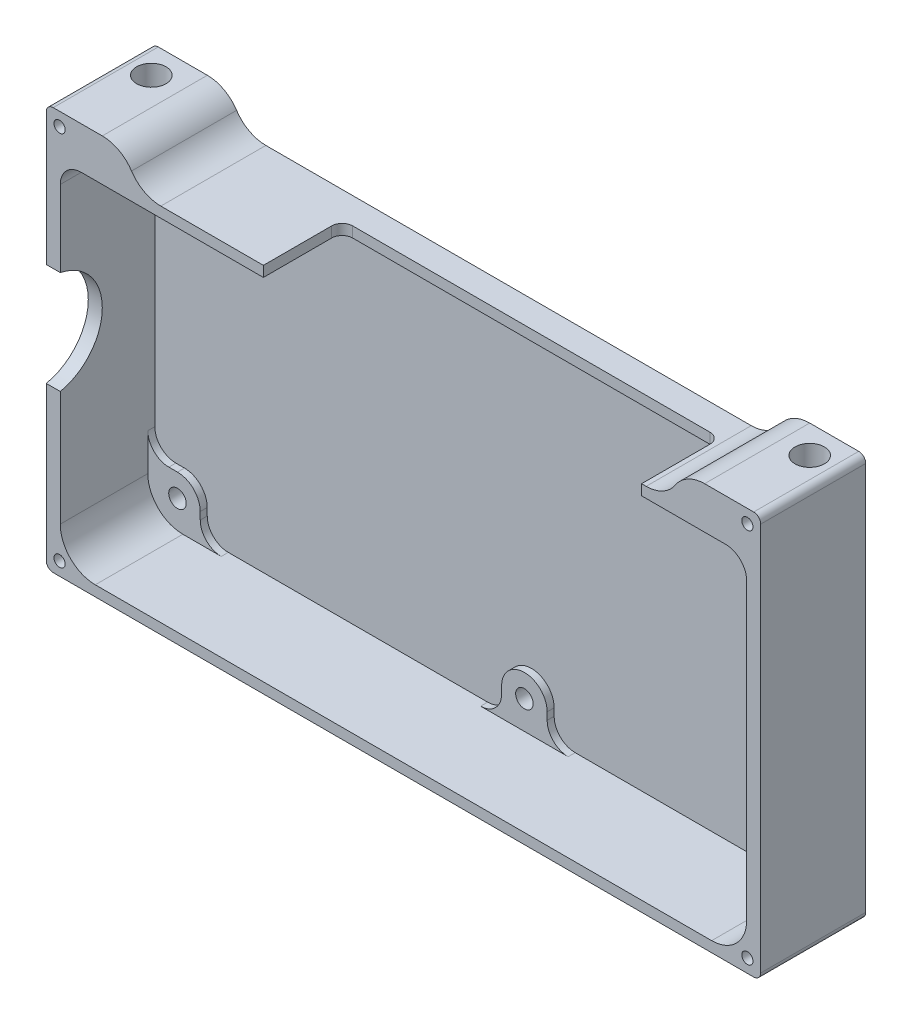
SolidWorks part; units mm, degrees
ref_plane "Ebene vorne" through (0, 0, 0) normal (0, 0, 1) x (1, 0, 0)
ref_plane "Ebene oben" through (0, 0, 0) normal (0, 1, 0) x (1, 0, 0)
ref_plane "Ebene rechts" through (0, 0, 0) normal (1, 0, 0) x (0, 0, -1)
sketch "Skizze1" plane through (0, 0, 0) normal (0, 0, 1) x (1, 0, 0)
  line L1 (0, 0) -> (102, 0)
  line L2 (0, 0) -> (0, 57.5)
  line L3 (0, 57.5) -> (102, 57.5)
  line L4 (102, 0) -> (102, 57.5)
  line L5 (2, 51.5) -> (100, 51.5) construction
  line L6 (2, 51.5) -> (2, 1.5)
  line L7 (2, 1.5) -> (100, 1.5) construction
  line L8 (100, 51.5) -> (100, 1.5) construction
  dimension "D1" = 2
  dimension "D2" = 2
  dimension "D3" = 6
  dimension "D4" = 1.5
  dimension "D5" = 50
  dimension "D6" = 98
extrude "Aufsatz-Linear austragen1" add sketch "Skizze1" along normal blind 15 contours L8 L5 L6 L7 | L2 L3 L4 L1
sketch "Skizze4" plane through (0, 0, 15) normal (0, 0, 1) x (1, 0, 0)
  line L0 (0, 57.5) -> (102, 57.5) construction
  line L1 (2, 51.5) -> (100, 51.5)
  line L2 (2, 51.5) -> (2, 1.5)
  line L3 (2, 1.5) -> (100, 1.5)
  line L4 (100, 51.5) -> (100, 1.5)
  line L5 (0, 0) -> (0, 57.5) construction
  line L6 (102, 0) -> (102, 57.5) construction
  line L7 (0, 0) -> (102, 0) construction
  dimension "D1" = 6
  dimension "D2" = 2
  dimension "D3" = 2
  dimension "D4" = 1.5
extrude "Schnitt-Linear austragen1" cut sketch "Skizze4" against normal blind 13.5
sketch "Skizze5" plane through (0, 0, 1.5) normal (0, 0, 1) x (1, 0, 0)
  line L0 (2, 1.5) -> (100, 1.5) construction
  line L2 (98.945, 50.63) -> (98.945, 51.5) construction
  line L3 (3.055, 2.37) -> (98.945, 2.37) construction
  line L4 (3.055, 2.37) -> (3.055, 50.63) construction
  line L5 (3.055, 50.63) -> (98.945, 50.63) construction
  line L6 (98.945, 2.37) -> (98.945, 50.63) construction
  line L7 (100, 51.5) -> (2, 51.5) construction
  line L8 (98.945, 2.37) -> (98.945, 1.5) construction
  line L9 (3.055, 50.63) -> (2, 50.63) construction
  line L10 (2, 51.5) -> (2, 1.5) construction
  line L11 (98.945, 50.63) -> (100, 50.63) construction
  line L12 (100, 1.5) -> (100, 51.5) construction
  line L13 (6.235, 5.55) -> (55.765, 5.55) construction
  line L14 (55.765, 5.55) -> (95.765, 5.55) construction
  line L15 (95.765, 5.55) -> (95.765, 47.45) construction
  line L16 (95.765, 47.45) -> (6.235, 47.45) construction
  line L17 (6.235, 47.45) -> (6.235, 5.55) construction
  circle A0 centre (6.235, 5.55) radius 3.25
  circle A1 centre (55.765, 5.55) radius 3.25
  circle A2 centre (95.765, 5.55) radius 3.25
  circle A3 centre (95.765, 47.45) radius 3.25
  circle A4 centre (6.235, 47.45) radius 3.25
  dimension "D8" = 6.5
  dimension "D1" = 3.18
  dimension "D2" = 3.18
  dimension "D3" = 92.71
  dimension "D4" = 95.89
  dimension "D5" = 48.26
  dimension "D6" = 52.71
  dimension "D7" = 3.18
extrude "Aufsatz-Linear austragen2" add sketch "Skizze5" along normal blind 1
sketch "Skizze11" plane through (0, 0, 0) normal (-1, 0, 0) x (0, 0, 1)
  line L0 (15, 0) -> (15, 57.5) construction
  line L2 (16.5, 37.75) -> (16.5, 22.75)
  line L5 (2.5, 44.2) -> (2.5, 50.7) construction
  line L6 (2.5, 44.2) -> (2.5, 50.7) construction
  arc A0 (16.5, 37.75) -> (16.5, 22.75) centre (16.5, 30.25) ccw
  point P11 (2.5, 47.45)
  dimension "D1" = 7.5
  dimension "D2" = 17.2
  dimension "D3" = 1.5
extrude "Schnitt-Linear austragen3" cut sketch "Skizze11" against normal up to next
sketch "Skizze12" plane through (0, 57.5, 0) normal (0, 1, 0) x (1, 0, 0)
  line L0 (85, -5.25) -> (85, -15)
  line L1 (0, -15) -> (102, -15) construction
  line L2 (85, -15) -> (31, -15)
  line L3 (31, -15) -> (31, -5.25)
  line L4 (32.5, -3.75) -> (83.5, -3.75)
  line L6 (92.515, -2.5) -> (99.015, -2.5) construction
  line L7 (92.515, -2.5) -> (99.015, -2.5) construction
  arc A0 (31, -5.25) -> (32.5, -3.75) centre (32.5, -5.25) cw
  arc A1 (85, -5.25) -> (83.5, -3.75) centre (83.5, -5.25) ccw
  point P11 (95.765, -2.5)
  dimension "D1" = 1.5
  dimension "D2" = 10.765
  dimension "D3" = 54
  dimension "D4" = 11.25
extrude "Schnitt-Linear austragen4" cut sketch "Skizze12" against normal up to next
sketch "Skizze13" plane through (0, 0, 1.5) normal (0, 0, 1) x (1, 0, 0)
  line L0 (6.235, 44.2) -> (2, 44.2)
  line L1 (9.485, 47.45) -> (9.485, 51.5)
  line L2 (9.485, 5.55) -> (9.485, 1.5)
  line L3 (6.235, 8.8) -> (2, 8.8)
  line L4 (2, 51.5) -> (2, 1.5)
  line L5 (2, 1.5) -> (100, 1.5)
  line L6 (100, 1.5) -> (100, 51.5)
  line L7 (100, 51.5) -> (2, 51.5)
  line L8 (2, 51.5) -> (2, 44.2)
  line L9 (2, 1.5) -> (9.485, 1.5)
  line L10 (100, 1.5) -> (100, 8.8)
  line L11 (100, 51.5) -> (92.515, 51.5)
  line L12 (59.015, 5.55) -> (59.015, 1.5)
  line L13 (52.515, 5.55) -> (52.515, 1.5)
  line L14 (95.765, 8.8) -> (100, 8.8)
  line L15 (92.515, 5.55) -> (92.515, 1.5)
  line L16 (92.515, 47.45) -> (92.515, 51.5)
  line L17 (95.765, 44.2) -> (100, 44.2)
  line L18 (9.485, 51.5) -> (2, 51.5)
  line L19 (100, 44.2) -> (100, 51.5)
  line L20 (92.515, 1.5) -> (100, 1.5)
  line L21 (52.515, 1.5) -> (59.015, 1.5)
  line L22 (2, 8.8) -> (2, 1.5)
  circle A0 centre (6.235, 47.45) radius 3.25 construction
  arc A1 (6.235, 44.2) -> (9.485, 47.45) centre (6.235, 47.45) ccw
  circle A2 centre (6.235, 5.55) radius 3.25 construction
  arc A3 (9.485, 5.55) -> (6.235, 8.8) centre (6.235, 5.55) ccw
  circle A4 centre (95.765, 5.55) radius 3.25 construction
  circle A5 centre (55.765, 5.55) radius 3.25 construction
  arc A6 (95.765, 8.8) -> (92.515, 5.55) centre (95.765, 5.55) ccw
  arc A7 (59.015, 5.55) -> (52.515, 5.55) centre (55.765, 5.55) ccw
  circle A8 centre (95.765, 47.45) radius 3.25 construction
  arc A9 (92.515, 47.45) -> (95.765, 44.2) centre (95.765, 47.45) ccw
  dimension "D1" = 0
extrude "Aufsatz-Linear austragen3" add sketch "Skizze13" along normal up to surface (1 mm away) up to face at (9.485, 47.45, 2.5)
hole_wizard "M3 Gewindebohrung1" positions "Skizze9" profile "Skizze8" tap size "M3" standard "DIN" end condition through all
sketch "Skizze9" plane through (0, 0, 2.5) normal (0, 0, 1) x (1, 0, 0)
  point P0 (6.235, 47.45)
  point P3 (6.235, 5.55)
  point P6 (55.765, 5.55)
  point P9 (95.765, 47.45)
  point P12 (95.765, 5.55)
sketch "Skizze8" plane through (6.235, 47.45, 2.5) normal (1, 0, 0) x (0, -1, 0)
  line L0 (0, 0) -> (0, 2.5)
  line L1 (0, 2.5) -> (1.25, 2.5)
  line L2 (1.25, 2.5) -> (1.25, 0)
  line L5 (1.25, 0) -> (0, 0)
  line L11 (0, -6.35) -> (0, 107.95) construction
  dimension "Bohrerdurchmesser" = 2.5
  dimension "Bohrungstiefe" = 2.5
cosmetic thread "Bohrungsgewinde3" parameters "D2"=3
cosmetic thread "Bohrungsgewinde4" parameters "D2"=3
cosmetic thread "Bohrungsgewinde5" parameters "D2"=3
cosmetic thread "Bohrungsgewinde6" parameters "D2"=3
cosmetic thread "Bohrungsgewinde7" parameters "D2"=3
hole_wizard "Gewindebohrung für M4x0.7 Helicoil1" positions "Skizze7" profile "Skizze6" tap size "M4x0.7" standard "Helicoil® Metrisch"
sketch "Skizze7" plane through (38.5152, 57.5, 4.646) normal (0, -1, 0) x (-1, 0, 0)
  line L0 (34.5152, 0.646) -> (-59.4848, 0.646)
  line L4 (38.5152, 4.646) -> (-63.4848, 4.646) construction
  line L5 (38.5152, -10.354) -> (38.5152, 4.646) construction
  line L6 (-63.4848, -10.354) -> (-63.4848, 4.646) construction
  point P0 (34.5152, 0.646)
  point P2 (-59.4848, 0.646)
  dimension "D1" = 4
  dimension "D2" = 4
  dimension "D3" = 4
sketch "Skizze6" plane through (4, 57.5, 4) normal (1, 0, 0) x (0, 0, 1)
  line L0 (0, 0) -> (0, 5.2618)
  line L1 (0, 5.2618) -> (2.1, 4)
  line L2 (2.1, 4) -> (2.1, 0)
  line L5 (2.1, 0) -> (0, 0)
  line L10 (0, 5.2618) -> (-2.1, 4) construction
  line L11 (0, -6.35) -> (0, 107.95) construction
  dimension "Bohrerdurchmesser" = 4.2
  dimension "Bohrungstiefe" = 4
  dimension "Spitzenwinkel" = 118
cosmetic thread "Bohrungsgewinde12" parameters "D1"=0, "D2"=5.2
cosmetic thread "Bohrungsgewinde13" parameters "D1"=0, "D2"=5.2
fillet "Verrundung1" radius 5 2 edges at (2, 1.5, 8.75) (100, 1.5, 8.75)
fillet "Verrundung2" radius 3 10 edges at (92.515, 51.5, 2) (100, 44.2, 2) (100, 8.8, 2) (92.515, 1.5, 2) (59.015, 1.5, 2) (52.515, 1.5, 2) (2, 8.8, 2) (9.485, 1.5, 2) (2, 44.2, 2) (9.485, 51.5, 2)
fillet "Verrundung3" radius 1 4 edges at (0, 57.5, 7.5) (102, 57.5, 7.5) (102, 0, 7.5) (0, 0, 7.5)
ref_plane "Ebene1" through (51, 0, 0) normal (-1, 0, 0) x (0, 0, 1)
fillet "Verrundung4" radius 3 2 edges at (100, 51.5, 8.75) (2, 51.5, 8.75)
hole_wizard "M2 Gewindebohrung1" positions "Skizze18" profile "Skizze17" tap size "M2" standard "DIN"
sketch "Skizze18" plane through (0, 0, 15) normal (0, 0, 1) x (1, 0, 0)
  line L0 (1, 57.5) -> (31, 57.5) construction
  line L1 (0, 37.5985) -> (0, 56.5) construction
  line L2 (85, 57.5) -> (101, 57.5) construction
  line L3 (102, 1) -> (102, 56.5) construction
  line L4 (1, 0) -> (101, 0) construction
  line L5 (0, 1) -> (0, 22.9015) construction
  line L6 (1, 0) -> (101, 0) construction
  circle A0 centre (1.9, 55.6) radius 1.9
  circle A1 centre (100.1, 55.6) radius 1.9
  circle A2 centre (100.1, 1.9) radius 1.9
  circle A3 centre (1.9, 1.9) radius 1.9
  point P1 (1.9, 55.6)
  point P11 (100.1, 55.6)
  point P13 (100.1, 1.9)
  point P15 (1.9, 1.9)
  dimension "D1" = 3.8
sketch "Skizze17" plane through (1.9, 55.6, 15) normal (1, 0, 0) x (0, -1, 0)
  line L0 (0, 0) -> (0, 6.4807)
  line L1 (0, 6.4807) -> (0.8, 6)
  line L2 (0.8, 6) -> (0.8, 0)
  line L5 (0.8, 0) -> (0, 0)
  line L10 (0, 6.4807) -> (-0.8, 6) construction
  line L11 (0, -6.35) -> (0, 107.95) construction
  dimension "Bohrerdurchmesser" = 1.6
  dimension "Bohrungstiefe" = 6
  dimension "Spitzenwinkel" = 118
cosmetic thread "Bohrungsgewinde8" parameters "D1"=4, "D2"=2
cosmetic thread "Bohrungsgewinde9" parameters "D1"=4, "D2"=2
cosmetic thread "Bohrungsgewinde10" parameters "D1"=4, "D2"=2
cosmetic thread "Bohrungsgewinde11" parameters "D1"=4, "D2"=2
sketch "Skizze19" plane through (0, 0, 15) normal (0, 0, 1) x (1, 0, 0)
  line L0 (94, 57.5) -> (8, 57.5)
  line L1 (85, 57.5) -> (101, 57.5) construction
  line L2 (1, 57.5) -> (31, 57.5) construction
  line L3 (16.3516, 53) -> (85.6484, 53)
  line L5 (31, 51.5) -> (5, 51.5) construction
  line L6 (0, 37.5985) -> (0, 56.5) construction
  line L7 (102, 1) -> (102, 56.5) construction
  arc A0 (94, 57.5) -> (89.8242, 55.25) centre (94, 52.5) ccw
  arc A1 (85.6484, 53) -> (89.8242, 55.25) centre (85.6484, 58) ccw
  arc A2 (12.1758, 55.25) -> (8, 57.5) centre (8, 52.5) ccw
  arc A3 (16.3516, 53) -> (12.1758, 55.25) centre (16.3516, 58) cw
  dimension "D1" = 5
  dimension "D2" = 1.5
  dimension "D3" = 8
  dimension "D4" = 8
extrude "Schnitt-Linear austragen5" cut sketch "Skizze19" against normal through all
sketch "Skizze20" plane through (0, 0, 0) normal (0, 0, -1) x (-1, 0, 0)
  line L0 (-51, 0) -> (-51, -8) construction
  line L1 (-1, 0) -> (-101, 0) construction
  line L2 (-47, -8) -> (-51, -8)
  line L3 (-51, -8) -> (-55, -8)
  line L4 (-47, -8) -> (-47, 0)
  line L5 (-47, 0) -> (-55, 0)
  line L6 (-55, -8) -> (-55, 0)
  circle A0 centre (-51, -4) radius 2.25
  dimension "D3" = 4.5
  dimension "D1" = 8
  dimension "D2" = 8
extrude "Aufsatz-Linear austragen4" add sketch "Skizze20" against normal blind 3
fillet "Verrundung5" radius 3 4 edges at (55, 0, 1.5) (47, 0, 1.5) (47, -8, 1.5) (55, -8, 1.5)
